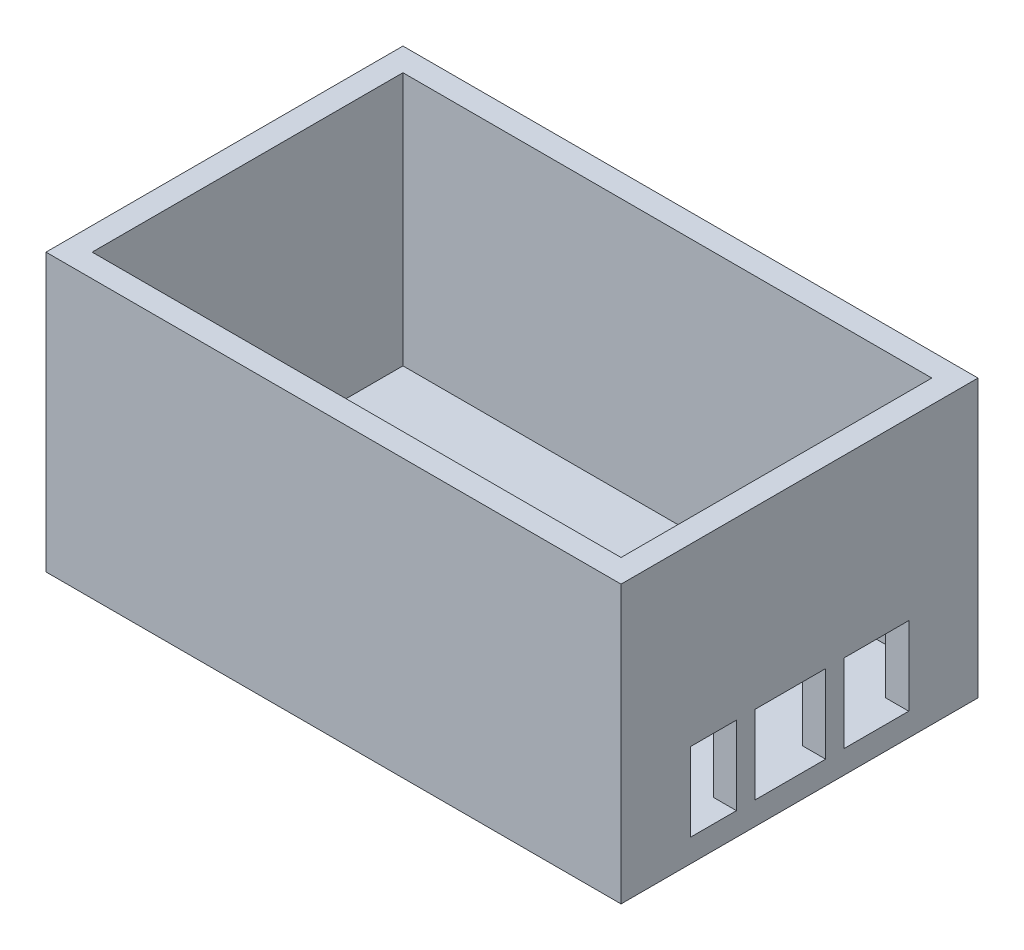
SolidWorks part; units mm, degrees
ref_plane "Front Plane" through (0, 0, 0) normal (0, 0, 1) x (1, 0, 0)
ref_plane "Top Plane" through (0, 0, 0) normal (0, 1, 0) x (1, 0, 0)
ref_plane "Right Plane" through (0, 0, 0) normal (1, 0, 0) x (0, 0, -1)
sketch "Sketch1" plane through (0, 0, 0) normal (0, 1, 0) x (1, 0, 0)
  line L1 (-79.1, 49.1) -> (79.1, 49.1)
  line L2 (-79.1, 49.1) -> (-79.1, -49.1)
  line L3 (-79.1, -49.1) -> (79.1, -49.1)
  line L4 (79.1, 49.1) -> (79.1, -49.1)
  line L5 (-79.1, 49.1) -> (79.1, -49.1) construction
  line L6 (-79.1, -49.1) -> (79.1, 49.1) construction
  point P0 (0, 0)
  dimension "D1" = 158.2
  dimension "D2" = 98.2
extrude "Boss-Extrude1" add sketch "Sketch1" along normal blind 6.35
sketch "Sketch2" plane through (0, 0, 49.1) normal (0, 0, 1) x (1, 0, 0)
  line L1 (-79.1, 76.2) -> (79.1, 76.2)
  line L2 (-79.1, 76.2) -> (-79.1, 6.35)
  line L3 (-79.1, 6.35) -> (79.1, 6.35)
  line L4 (79.1, 76.2) -> (79.1, 6.35)
  line L5 (-79.1, 76.2) -> (79.1, 6.35) construction
  line L6 (-79.1, 6.35) -> (79.1, 76.2) construction
  point P0 (0, 41.275)
  dimension "D1" = 69.85
extrude "Boss-Extrude2" add sketch "Sketch2" against normal blind 6.35
sketch "Sketch3" plane through (-79.1, 0, 0) normal (-1, 0, 0) x (0, 0, 1)
  line L1 (-42.75, 76.2) -> (42.75, 76.2)
  line L2 (-42.75, 76.2) -> (-42.75, 6.35)
  line L3 (-42.75, 6.35) -> (42.75, 6.35)
  line L4 (42.75, 76.2) -> (42.75, 6.35)
  line L5 (-42.75, 76.2) -> (42.75, 6.35) construction
  line L6 (-42.75, 6.35) -> (42.75, 76.2) construction
  point P0 (0, 41.275)
  dimension "D1" = 69.85
extrude "Boss-Extrude3" add sketch "Sketch3" against normal blind 6.35
sketch "Sketch4" plane through (0, 0, -49.1) normal (0, 0, -1) x (-1, 0, 0)
  line L1 (-79.1, 76.2) -> (79.1, 76.2)
  line L2 (-79.1, 76.2) -> (-79.1, 6.35)
  line L3 (-79.1, 6.35) -> (79.1, 6.35)
  line L4 (79.1, 76.2) -> (79.1, 6.35)
  line L5 (-79.1, 76.2) -> (79.1, 6.35) construction
  line L6 (-79.1, 6.35) -> (79.1, 76.2) construction
  point P0 (0, 41.275)
  dimension "D1" = 69.85
extrude "Boss-Extrude4" add sketch "Sketch4" against normal blind 6.35
sketch "Sketch5" plane through (79.1, 0, 0) normal (1, 0, 0) x (0, 0, -1)
  line L0 (42.75, 76.2) -> (42.75, 6.35) construction
  line L1 (-42.75, 27.94) -> (42.75, 27.94)
  line L2 (-42.75, 27.94) -> (-42.75, 76.2)
  line L3 (-42.75, 76.2) -> (42.75, 76.2)
  line L4 (42.75, 27.94) -> (42.75, 76.2)
  line L5 (-42.75, 27.94) -> (42.75, 76.2) construction
  line L6 (-42.75, 76.2) -> (42.75, 27.94) construction
  line L7 (42.75, 76.2) -> (42.75, 6.35) construction
  line L8 (42.75, 76.2) -> (49.1, 76.2) construction
  point P0 (0, 52.07)
  dimension "D1" = 48.26
  dimension "D2" = 0
extrude "Boss-Extrude5" add sketch "Sketch5" against normal blind 6.35
sketch "Sketch6" plane through (79.1, 0, 0) normal (1, 0, 0) x (0, 0, -1)
  line L0 (-42.75, 27.94) -> (42.75, 27.94) construction
  line L1 (-17.35, 27.94) -> (-12.27, 27.94)
  line L2 (-17.35, 27.94) -> (-17.35, 6.35)
  line L3 (-17.35, 6.35) -> (-12.27, 6.35)
  line L4 (-12.27, 27.94) -> (-12.27, 6.35)
  line L5 (-42.75, 6.35) -> (42.75, 6.35) construction
  line L6 (42.75, 6.35) -> (-42.75, 6.35) construction
  line L7 (7.19, 27.94) -> (12.27, 27.94)
  line L8 (7.19, 27.94) -> (7.19, 6.35)
  line L9 (7.19, 6.35) -> (12.27, 6.35)
  line L10 (12.27, 27.94) -> (12.27, 6.35)
  line L11 (-42.75, 6.35) -> (-42.75, 27.94) construction
  line L12 (42.75, 27.94) -> (42.75, 6.35) construction
  line L14 (-42.75, 27.94) -> (-30.05, 27.94)
  line L15 (-42.75, 27.94) -> (-42.75, 6.35)
  line L16 (-42.75, 6.35) -> (-30.05, 6.35)
  line L17 (-30.05, 27.94) -> (-30.05, 6.35)
  line L18 (42.75, 27.94) -> (30.05, 27.94)
  line L19 (42.75, 27.94) -> (42.75, 6.35)
  line L20 (42.75, 6.35) -> (30.05, 6.35)
  line L21 (30.05, 27.94) -> (30.05, 6.35)
  dimension "D1" = 5.08
  dimension "D2" = 5.08
  dimension "D3" = 25.4
  dimension "D4" = 30.48
  dimension "D5" = 0
  dimension "D6" = 12.7
  dimension "D7" = 12.7
extrude "Boss-Extrude6" add sketch "Sketch6" against normal blind 6.35
